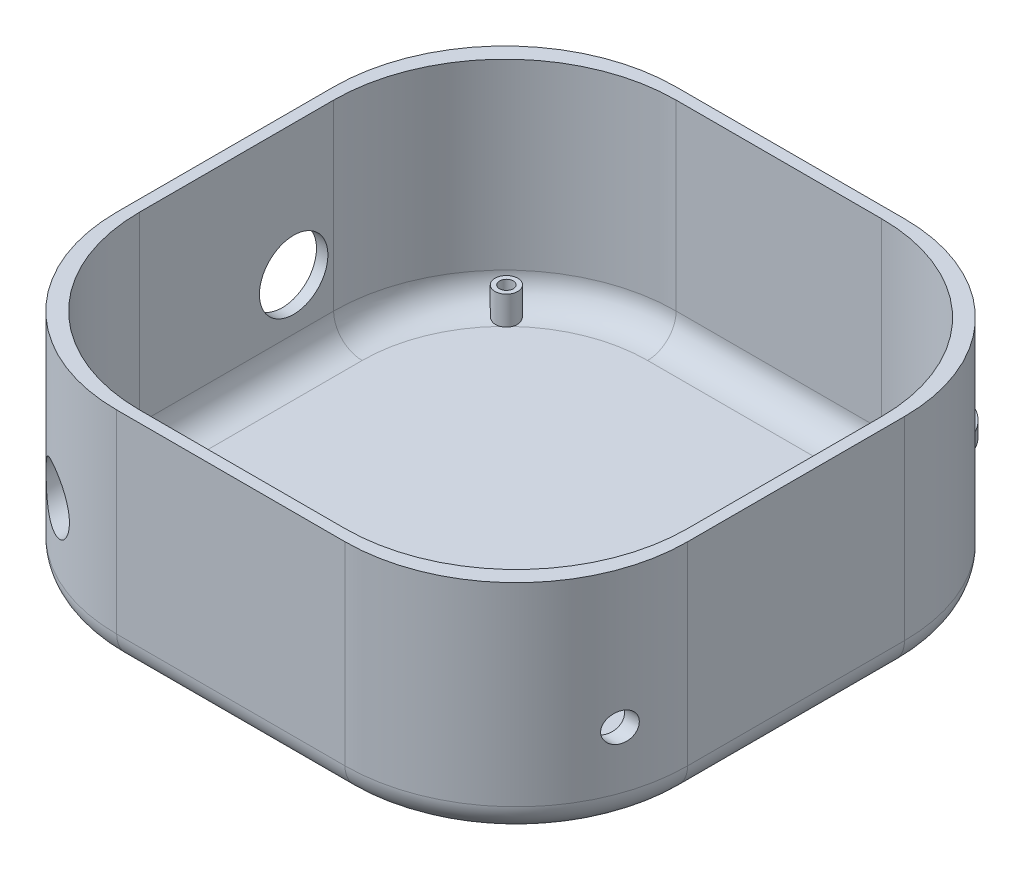
SolidWorks part; units mm, degrees
ref_plane "Front Plane" through (0, 0, 0) normal (0, 0, 1) x (1, 0, 0)
ref_plane "Top Plane" through (0, 0, 0) normal (0, 1, 0) x (1, 0, 0)
ref_plane "Right Plane" through (0, 0, 0) normal (1, 0, 0) x (0, 0, -1)
sketch "Sketch7" plane through (0, 0, 0) normal (0, 0, 1) x (1, 0, 0)
  line L0 (112.4786, 252.5672) -> (795.1453, 252.5672) construction
sketch "Sketch6" plane through (0, 0, 0) normal (1, 0, 0) x (0, 0, -1)
  line L0 (106.6139, 222.2744) -> (789.2806, 222.2744) construction
sketch "Sketch4" plane through (0, 0, 0) normal (0, 1, 0) x (1, 0, 0)
  line L0 (102.2144, 571.953) -> (742.2144, 571.953) construction
sketch "Sketch1" plane through (0, 0, 0) normal (0, 1, 0) x (1, 0, 0)
  line L0 (163.1224, 741.5892) -> (896.4526, 741.5892) construction
  line L1 (-18.1542, 55.1613) -> (-18.1542, 48.8848)
  line L2 (-20, -49) -> (20, -49)
  line L3 (-50, -19) -> (-50, 19)
  line L4 (-20, 49) -> (20, 49)
  line L5 (50, -19) -> (50, 19)
  line L6 (-50, -49) -> (50, 49) construction
  line L7 (-50, 49) -> (50, -49) construction
  line L8 (-18, -47) -> (18, -47)
  line L9 (-48, -17) -> (-48, 17)
  line L10 (-18, 47) -> (18, 47)
  line L11 (48, -17) -> (48, 17)
  line L12 (-48, -47) -> (48, 47) construction
  line L13 (-48, 47) -> (48, -47) construction
  line L15 (-5.5164, 55.1613) -> (-5.5164, 49)
  line L16 (-5.5164, 49) -> (-10.4584, 48.955)
  line L17 (-23.0961, 48.8398) -> (-23.0961, 55.1613)
  line L18 (-10.4584, 55.1613) -> (-10.4584, 49)
  line L20 (-10.4584, 49) -> (-10.4584, 48.955)
  line L21 (0, 0) -> (0, 63.1182)
  line L23 (5.5164, 55.1613) -> (5.5164, 49)
  line L24 (23.0961, 48.8398) -> (23.0961, 55.1613)
  line L25 (10.4584, 55.1613) -> (10.4584, 49)
  line L26 (18.1542, 55.1613) -> (18.1542, 48.8848)
  line L27 (5.5164, 49) -> (10.4584, 48.955)
  line L28 (-18.1542, 48.8848) -> (-23.0961, 48.8398)
  line L29 (10.4584, 49) -> (10.4584, 48.955)
  line L30 (18.1542, 48.8848) -> (23.0961, 48.8398)
  arc A0 (-48, 17) -> (-18, 47) centre (-18, 17) cw
  arc A1 (-18, -47) -> (-48, -17) centre (-18, -17) cw
  arc A2 (18, -47) -> (48, -17) centre (18, -17) ccw
  arc A3 (48, 17) -> (18, 47) centre (18, 17) ccw
  arc A4 (-50, -19) -> (-20, -49) centre (-20, -19) ccw
  arc A5 (20, -49) -> (50, -19) centre (20, -19) ccw
  arc A6 (50, 19) -> (20, 49) centre (20, 19) ccw
  arc A7 (-50, 19) -> (-20, 49) centre (-20, 19) cw
  circle A8 centre (-36.8433, 36.1065) radius 2
  circle A9 centre (-36.8433, 36.1065) radius 1.2
  circle A10 centre (36.1065, 36.8433) radius 1.2
  circle A11 centre (36.1065, 36.8433) radius 2
  circle A12 centre (36.8433, -36.1065) radius 1.2
  circle A13 centre (36.8433, -36.1065) radius 2
  circle A14 centre (-36.1065, -36.8433) radius 1.2
  circle A15 centre (-36.1065, -36.8433) radius 2
  arc A16 (-10.4584, 55.1613) -> (-18.1542, 55.1613) centre (-14.3063, 55.1613) ccw
  arc A18 (-8.0602, 48.9768) -> (-8.0373, 49) centre (-14.3063, 55.1613) ccw
  arc A19 (-5.5164, 55.1613) -> (-23.0961, 55.1613) centre (-14.3063, 55.1613) ccw
  arc A20 (5.5164, 55.1613) -> (23.0961, 55.1613) centre (14.3063, 55.1613) cw
  arc A21 (10.4584, 55.1613) -> (18.1542, 55.1613) centre (14.3063, 55.1613) cw
  point P2 (0, 0)
  point P8 (0, 0)
  dimension "D5" = 30
  dimension "D6" = 30
  dimension "D7" = 30
  dimension "D8" = 2.4
  dimension "D9" = 4
  dimension "D10" = 4
  dimension "D1" = 98
  dimension "D2" = 100
  dimension "D3" = 96
  dimension "D4" = 94
extrude "Boss-Extrude1" add sketch "Sketch1" along normal blind 39 contours A7 L4 A6 L5 A5 L2 A4 L3
extrude "Cut-Extrude1" cut sketch "Sketch1<3>" along normal blind 39 from offset 2 contours L11 A3 L10 A0 L9 A1 L8 A2
sketch "Sketch1<3>" plane through (0, 0, 0) normal (0, 1, 0) x (1, 0, 0) same geometry as "Sketch1"
extrude "Boss-Extrude2" add sketch "Sketch1<4>" along normal blind 7 contours A13 | A11 | A10 | A8 | A9 | A15 | A14 | A12
sketch "Sketch1<4>" plane through (0, 0, 0) normal (0, 1, 0) x (1, 0, 0) same geometry as "Sketch1"
extrude "Boss-Extrude3" add sketch "Sketch1<5>" along normal blind 2.5 contours A19 L17 L28 L1 A16 L18 L20 L16 L15 | L27 L29 L25 A21 L26 L30 L24 A20 L23
sketch "Sketch1<5>" plane through (0, 0, 0) normal (0, 1, 0) x (1, 0, 0) same geometry as "Sketch1"
fillet "Fillet1" radius 5 8 edges at (48, 2, 0) (39.2132, 2, 38.2132) (0, 2, 47) (-39.2132, 2, 38.2132) (39.2132, 2, -38.2132) (0, 2, -47) (-39.2132, 2, -38.2132) (-48, 2, 0)
fillet "Fillet4" radius 5 4 edges at (19.0771, 2.5, -49) (21.5501, 2.5, -48.9599) (-21.5501, 2.5, -48.9599) (-19.0771, 2.5, -49)
fillet "Fillet2" radius 5 7 edges at (41.2132, 0, 40.2132) (0, 0, 49) (-41.2132, 0, 40.2132) (-50, 0, 0) (-42.281, 0, -39.0888) (42.281, 0, -39.0888) (50, 0, 0)
fillet "Fillet5" radius 5 2 edges at (7.9874, 2.5, -49) (-7.9874, 2.5, -49)
fillet "Fillet6" radius 5 3 edges at (14.3063, 0, -49) (0, 0, -49) (-14.3063, 0, -49)
sketch "Sketch2" plane through (0, 0, 0) normal (1, 0, 0) x (0, 0, -1)
  circle A0 centre (-29, 15) radius 2.5
  circle A1 centre (10, 16) radius 6
  dimension "D1" = 10
extrude "Cut-Extrude2" cut sketch "Sketch2" against normal blind 50 contours A1
sketch "Sketch3" plane through (0, 0, 0) normal (0, 0, 1) x (1, 0, 0)
  circle A0 centre (-35, 16) radius 5
  dimension "D1" = 10
  dimension "D2" = 35
  dimension "D3" = 16
extrude "Cut-Extrude5" cut sketch "Sketch2<4>" along normal blind 50 contours A0
sketch "Sketch2<4>" plane through (0, 0, 0) normal (1, 0, 0) x (0, 0, -1) same geometry as "Sketch2"
extrude "Cut-Extrude6" cut sketch "Sketch3" along normal blind 50 contours A0
